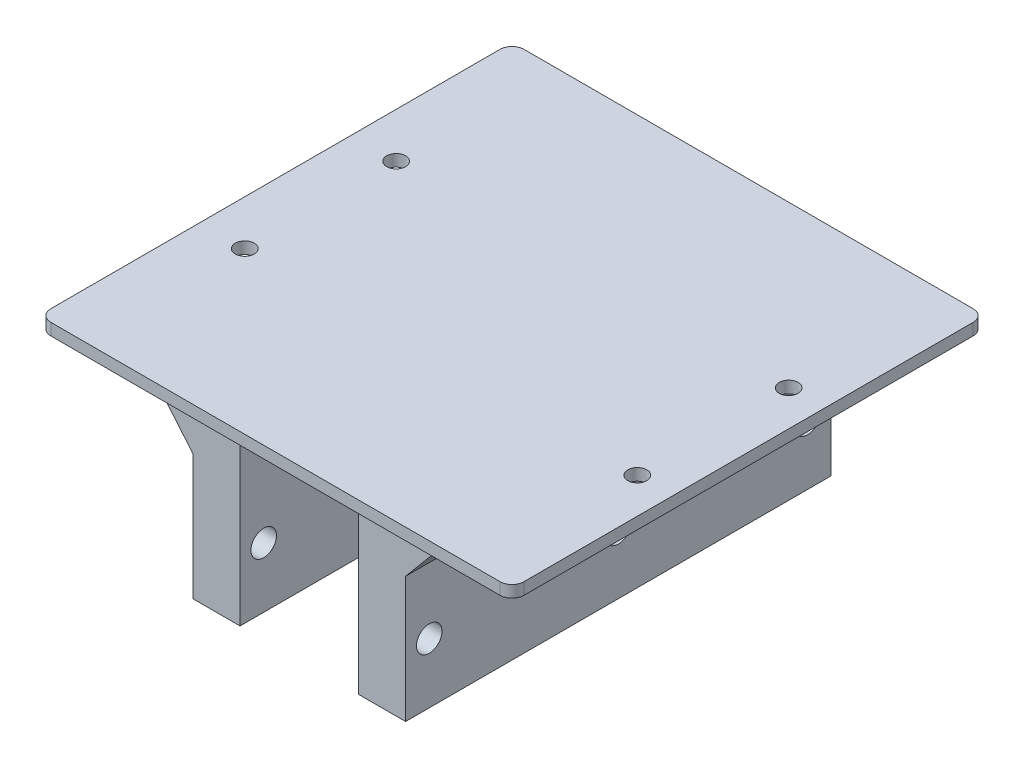
SolidWorks part; units mm, degrees
ref_plane "Front Plane" through (0, 0, 0) normal (0, 0, 1) x (1, 0, 0)
ref_plane "Top Plane" through (0, 0, 0) normal (0, 1, 0) x (1, 0, 0)
ref_plane "Right Plane" through (0, 0, 0) normal (1, 0, 0) x (0, 0, -1)
sketch "Sketch1" plane through (0, 0, 0) normal (0, 1, 0) x (1, 0, 0)
  line L1 (2.5, 0) -> (97.5, 0)
  line L2 (0, 2.5) -> (0, 97.5)
  line L3 (2.5, 100) -> (97.5, 100)
  line L4 (100, 2.5) -> (100, 97.5)
  circle A0 centre (9.5, 34) radius 2
  circle A1 centre (9.5, 66) radius 2
  arc A4 (97.5, 100) -> (100, 97.5) centre (97.5, 97.5) cw
  arc A5 (97.5, 0) -> (100, 2.5) centre (97.5, 2.5) ccw
  arc A6 (2.5, 0) -> (0, 2.5) centre (2.5, 2.5) cw
  arc A7 (0, 97.5) -> (2.5, 100) centre (2.5, 97.5) cw
  circle A8 centre (92.5, 66) radius 2
  circle A9 centre (92.5, 34) radius 2
  point P13 (0, 0)
  point P14 (88.5, 38)
  point P17 (100, 100)
  point P22 (0, 0)
  point P25 (0, 100)
  point P26 (0, 0)
  point P27 (88.5, 38)
  point P28 (0, 0)
  dimension "D1" = 4
  dimension "D7" = 2.5
  dimension "D8" = 83
  dimension "D2" = 100
  dimension "D3" = 100
  dimension "D4" = 32
  dimension "D5" = 34
  dimension "D6" = 9.5
extrude "Boss-Extrude1" add sketch "Sketch1" along normal blind 2.5
sketch "Sketch4" plane through (0, 0, 0) normal (0, 1, 0) x (1, 0, 0)
  line L0 (37.5, 50) -> (62.5, 50) construction
  line L1 (27.5, 5) -> (37.5, 5)
  line L2 (27.5, 5) -> (27.5, 95)
  line L3 (27.5, 95) -> (37.5, 95)
  line L4 (37.5, 5) -> (37.5, 95)
  line L5 (62.5, 95) -> (72.5, 95)
  line L6 (62.5, 95) -> (62.5, 5)
  line L7 (62.5, 5) -> (72.5, 5)
  line L8 (72.5, 95) -> (72.5, 5)
  line L9 (50, 100) -> (50, 0) construction
  line L10 (97.5, 100) -> (2.5, 100) construction
  line L11 (2.5, 0) -> (97.5, 0) construction
  point P16 (50, 50)
  point P17 (50, 50)
  dimension "D1" = 25
  dimension "D2" = 5
  dimension "D3" = 10
extrude "Boss-Extrude2" add sketch "Sketch4" against normal blind 38.1
sketch "Sketch5" plane through (27.5, 0, 0) normal (-1, 0, 0) x (0, 0, 1)
  line L0 (-95, -38.1) -> (-95, 0) construction
  line L2 (-95, 0) -> (-5, 0) construction
  circle A0 centre (-90, -25.4) radius 2.7
  circle A1 centre (-50, -25.4) radius 2.7
  circle A2 centre (-10, -25.4) radius 2.7
  point P8 (0, 0)
  point P9 (0, 0)
  dimension "D1" = 40
  dimension "D3" = 5.4
  dimension "D2" = 80
  dimension "D4" = 5
  dimension "D5" = 25.4
extrude "Cut-Extrude1" cut sketch "Sketch5" against normal through all
draft "Draft1" [suppressed] type of draft neutral plane draft angle 5 faces to draft 6 parameters "D1"=5
sketch "Sketch6" plane through (0, 0, -5) normal (0, 0, 1) x (1, 0, 0)
  line L0 (72.5, 0) -> (82.1418, 0)
  line L1 (2.5, 0) -> (97.5, 0) construction
  line L2 (82.1418, 0) -> (72.5, -11.4907)
  line L3 (72.5, -38.1) -> (72.5, 0) construction
  line L4 (72.5, -11.4907) -> (72.5, 0)
  line L5 (27.5, 0) -> (17.8582, 0)
  line L6 (17.8582, 0) -> (27.5, -11.4907)
  line L7 (27.5, -38.1) -> (27.5, 0) construction
  line L8 (27.5, -11.4907) -> (27.5, 0)
  point P11 (27.5, -4.9564)
  dimension "D1" = 15
  dimension "D2" = 50
extrude "Boss-Extrude3" add sketch "Sketch6" against normal up to surface (90 mm away) from surface up to face at (32.5, -19.05, -95) starting at face at (32.5, -19.05, -5)
